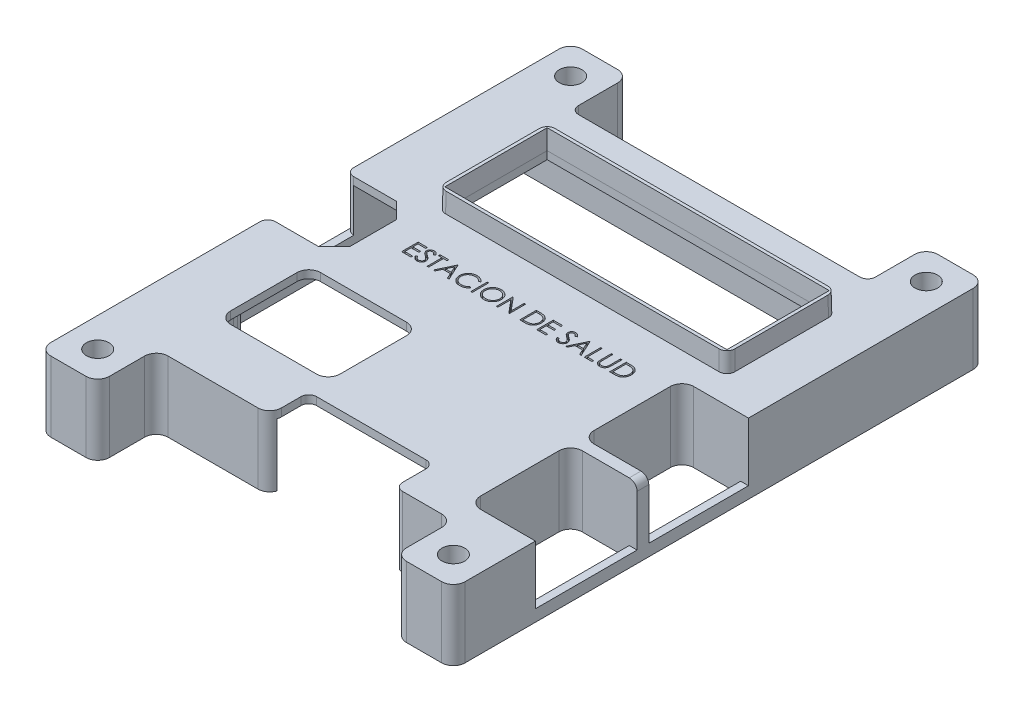
SolidWorks part; units mm, degrees
material "PVC 0.007 Plasticized"
ref_plane "Front Plane" through (0, 0, 0) normal (0, 0, 1) x (1, 0, 0)
ref_plane "Top Plane" through (0, 0, 0) normal (0, 1, 0) x (1, 0, 0)
ref_plane "Right Plane" through (0, 0, 0) normal (1, 0, 0) x (0, 0, -1)
sketch "Sketch1" plane through (0, 0, 0) normal (0, 1, 0) x (1, 0, 0)
  line L1 (-53, -53) -> (53, -53)
  line L2 (-53, -53) -> (-53, 53)
  line L3 (-53, 53) -> (53, 53)
  line L4 (53, -53) -> (53, 53)
  line L5 (-53, -53) -> (53, 53) construction
  line L6 (-53, 53) -> (53, -53) construction
  point P0 (0, 0)
  dimension "D1" = 106
  dimension "D2" = 106
extrude "Boss-Extrude1" add sketch "Sketch1" along normal blind 18
sketch "Sketch2" plane through (0, 18, 0) normal (0, 1, 0) x (1, 0, 0)
  line L0 (53, -53) -> (53, 53) construction
  line L1 (53, 7.5) -> (36, 7.5)
  line L2 (53, 7.5) -> (53, -18)
  line L3 (53, -18) -> (36, -18)
  line L4 (36, 7.5) -> (36, -18)
  line L5 (53, 53) -> (-53, 53) construction
  line L6 (-53, -53) -> (53, -53) construction
  dimension "D1" = 45.5
  dimension "D2" = 35
  dimension "D3" = 17
extrude "Cut-Extrude1" cut sketch "Sketch2" against normal through all
sketch "Sketch3" plane through (0, 18, 0) normal (0, 1, 0) x (1, 0, 0)
  line L0 (53, -53) -> (53, -18) construction
  line L1 (53, -21) -> (36, -21)
  line L2 (53, -21) -> (53, -47)
  line L3 (53, -47) -> (36, -47)
  line L4 (36, -21) -> (36, -47)
  line L5 (-53, -53) -> (53, -53) construction
  line L8 (36, -18) -> (53, -18) construction
  line L10 (36, 7.5) -> (36, -18) construction
  dimension "D1" = 6
  dimension "D2" = 3
extrude "Cut-Extrude2" cut sketch "Sketch3" against normal through all
shell "Shell1" thickness 2 removed face at (29.6667, 0, 13.0833)
sketch "Sketch5" plane through (-53, 0, 0) normal (-1, 0, 0) x (0, 0, 1)
  line L0 (-53, 0) -> (53, 0) construction
  line L1 (-10.5, 0) -> (9.5, 0)
  line L2 (-10.5, 0) -> (-10.5, 25)
  line L3 (-10.5, 25) -> (9.5, 25)
  line L4 (9.5, 0) -> (9.5, 25)
  line L5 (-53, 18) -> (-53, 0) construction
  dimension "D1" = 42.5
  dimension "D2" = 20
  dimension "D3" = 25
extrude "Cut-Extrude3" cut sketch "Sketch5" against normal blind 17
sketch "Sketch6" plane through (0, 0, 53) normal (0, 0, 1) x (1, 0, 0)
  line L0 (-53, 0) -> (53, 0) construction
  line L1 (-15, 0) -> (23, 0)
  line L2 (-15, 0) -> (-15, 18)
  line L3 (-15, 18) -> (23, 18)
  line L4 (23, 0) -> (23, 18)
  line L5 (53, 18) -> (53, 0) construction
  line L6 (-53, 18) -> (-53, 0) construction
  line L7 (-53, 18) -> (53, 18) construction
  dimension "D1" = 30
  dimension "D2" = 38
extrude "Cut-Extrude4" cut sketch "Sketch6" against normal blind 10
sketch "Sketch8" plane through (0, 18, 0) normal (0, 1, 0) x (1, 0, 0)
  line L0 (-9, -53) -> (-9, -15)
  line L1 (-9, -15) -> (-37, -15)
  line L2 (-9, -53) -> (-37, -53)
  line L3 (-37, -15) -> (-37, -53)
  line L6 (-53, 53) -> (-53, 10.5) construction
  line L7 (-53, -53) -> (-15, -53) construction
  line L10 (-53, -9.5) -> (-53, -53) construction
  dimension "D1" = 38
  dimension "D2" = 16
  dimension "D3" = 44
extrude "Cut-Extrude5" cut sketch "Sketch8" against normal through all
sketch "Sketch9" plane through (0, 18, 0) normal (0, 1, 0) x (1, 0, 0)
  line L0 (53, 53) -> (-53, 53) construction
  line L1 (-32, 41) -> (40, 41)
  line L2 (-32, 41) -> (-32, 15)
  line L3 (-32, 15) -> (40, 15)
  line L4 (40, 41) -> (40, 15)
  line L5 (53, 7.5) -> (53, 53) construction
  dimension "D1" = 72
  dimension "D2" = 26
  dimension "D3" = 12
  dimension "D4" = 13
extrude "Extrude-Thin1" add sketch "Sketch9" along normal blind 5 draft 1 thin thin type one direction wall 1
sketch "Sketch10" plane through (0, 18, 0) normal (0, 1, 0) x (1, 0, 0)
  line L8 (40, 41) -> (-32, 41)
  line L9 (-32, 41) -> (-32, 15)
  line L10 (-32, 15) -> (40, 15)
  line L11 (40, 15) -> (40, 41)
  line L12 (40, 41) -> (-32, 41)
  line L13 (-32, 41) -> (-32, 15)
  line L14 (-32, 15) -> (40, 15)
  line L15 (40, 15) -> (40, 41)
  dimension "D1" = 0
extrude "Cut-Extrude6" cut sketch "Sketch10" against normal up to next
chamfer "Chamfer1" distance 4 angle 45 2 edges at (-36, 17, -10.5) (-36, 17, 9.5)
sketch "Sketch12" plane through (0, 0, 0) normal (0, 1, 0) x (1, 0, 0)
  line L0 (0, 53) -> (0, -52.3512) construction
  line L1 (53, 53) -> (-53, 53) construction
  line L2 (-52.4973, 0) -> (53.7635, 0) construction
  line L15 (-38, 53) -> (-53, 53)
  line L16 (-53, 68) -> (-53, 53)
  line L17 (-38, 68) -> (-53, 68)
  line L18 (-38, 68) -> (-38, 53)
  line L32 (-53, 53) -> (-53, 10.5) construction
  line L33 (38, 68) -> (38, 53)
  line L34 (38, 68) -> (53, 68)
  line L35 (53, 68) -> (53, 53)
  line L36 (38, 53) -> (53, 53)
  line L37 (38, -53) -> (53, -53)
  line L38 (53, -68) -> (53, -53)
  line L39 (38, -68) -> (53, -68)
  line L40 (38, -68) -> (38, -53)
  line L41 (-38, -68) -> (-38, -53)
  line L42 (-38, -68) -> (-53, -68)
  line L43 (-53, -68) -> (-53, -53)
  line L44 (-38, -53) -> (-53, -53)
  dimension "D1" = 15
  dimension "D2" = 15
extrude "Boss-Extrude2" add sketch "Sketch12" along normal up to surface (18 mm away) up to face at (2.1667, 18, 15.6667)
sketch "Sketch13" plane through (0, 18, 0) normal (0, 1, 0) x (1, 0, 0)
  line L18 (-38, 53) -> (-53, 53) construction
  line L19 (-53, 68) -> (-53, 10.5) construction
  line L21 (-45.5, 68) -> (-45.5, 53) construction
  line L22 (-53, 68) -> (-38, 68) construction
  line L24 (0, -12.65) -> (0, 12.65) construction
  line L25 (-12.65, 0) -> (12.65, 0) construction
  circle A4 centre (-45.5, 60.5) radius 7.5 construction
  circle A5 centre (45.5, 60.5) radius 7.5 construction
  circle A6 centre (45.5, -60.5) radius 7.5 construction
  circle A7 centre (-45.5, -60.5) radius 7.5 construction
  point P54 (-45.5, 60.5)
  point P59 (45.5, 60.5)
  point P63 (45.5, -60.5)
  point P65 (-45.5, -60.5)
hole_wizard "M5 Clearance Hole1" positions "Sketch13" profile "Sketch14" hole size "M5" standard "ANSI Metric" end condition through all
sketch "Sketch14" plane through (-45.5, 18, 60.5) normal (1, 0, 0) x (0, 0, 1)
  line L0 (0, 0) -> (0, 18)
  line L1 (0, 18) -> (2.9, 18)
  line L2 (2.9, 18) -> (2.9, 0)
  line L5 (2.9, 0) -> (0, 0)
  line L11 (0, -6.35) -> (0, 107.95) construction
  dimension "Thru Hole Dia." = 5.8
  dimension "Thru Hole Depth" = 18
sketch "Sketch15" plane through (0, 18, 0) normal (0, 1, 0) x (1, 0, 0)
  line L0 (-9, -43) -> (-9, -15) construction
  line L1 (-9, -38) -> (-38, -38)
  line L2 (-9, -38) -> (-9, -53)
  line L3 (-9, -53) -> (-38, -53)
  line L4 (-38, -38) -> (-38, -53)
  line L5 (-38, -53) -> (-38, -68) construction
  line L6 (23, -43) -> (-9, -43) construction
  line L7 (-38, -53) -> (-37, -53) construction
  dimension "D1" = 5
extrude "Boss-Extrude3" add sketch "Sketch15" against normal up to surface (2 mm away) up to face at (4, 16, -28)
sketch "Sketch22" plane through (0, 16, 0) normal (0, -1, 0) x (1, 0, 0)
  line L1 (-37, 51) -> (-9, 51)
  line L2 (-37, 51) -> (-37, 53)
  line L3 (-37, 53) -> (-9, 53)
  line L4 (-9, 51) -> (-9, 53)
extrude "Boss-Extrude7" add sketch "Sketch22" along normal up to surface (16 mm away)
sketch "Sketch16" plane through (0, 18, 0) normal (0, 1, 0) x (1, 0, 0)
  line L0 (-36, 0) -> (36, 0) construction
  line L1 (-36, 6.5) -> (-36, -5.5) construction
  line L2 (36, 7.5) -> (36, -18) construction
  text T0 "ESTACION DE SALUD" font "Century Gothic" height in points 16
extrude "Cut-Extrude8" cut sketch "Sketch16" against normal blind 1.5
sketch "Sketch17" plane through (0, 16, 0) normal (0, -1, 0) x (1, 0, 0)
  line L0 (-51, 25.25) -> (-45, 25.25)
  line L1 (-51, 9.5) -> (-51, 51) construction
  line L2 (-43, 27.25) -> (-43, 28.25)
  line L3 (-45, 30.25) -> (-51, 30.25)
  line L4 (-51, 9.5) -> (-51, 51) construction
  line L5 (-51, 30.25) -> (-51, 25.25)
  arc A0 (-43, 28.25) -> (-45, 30.25) centre (-45, 28.25) ccw
  arc A1 (-45, 25.25) -> (-43, 27.25) centre (-45, 27.25) ccw
  point P5 (-40.3391, 29.0858)
  point P11 (-43, 30.25)
  point P14 (-43, 25.25)
  dimension "D3" = 2
  dimension "D1" = 5
  dimension "D2" = 8
extrude "Boss-Extrude4" add sketch "Sketch17" along normal up to surface (16 mm away)
sketch "Sketch19" plane through (-53, 0, 0) normal (-1, 0, 0) x (0, 0, 1)
  line L0 (-10.5, 18) -> (-10.5, 0) construction
  line L1 (-10.5, 5) -> (9.5, 5)
  line L2 (-10.5, 5) -> (-10.5, 0)
  line L3 (-10.5, 0) -> (9.5, 0)
  line L4 (9.5, 5) -> (9.5, 0)
  dimension "D1" = 5
extrude "Boss-Extrude5" add sketch "Sketch19" against normal up to surface (2 mm away) up to face at (-51, 8, -30.75)
sketch "Sketch20" plane through (53, 0, 0) normal (1, 0, 0) x (0, 0, -1)
  line L1 (-49.5, 3) -> (10.5, 3)
  line L2 (-49.5, 3) -> (-49.5, 0)
  line L3 (-49.5, 0) -> (10.5, 0)
  line L4 (10.5, 3) -> (10.5, 0)
  line L5 (7.5, 0) -> (-18, 0) construction
  line L6 (-19.5, 18) -> (-19.5, 0) construction
  line L7 (-21, 18) -> (-18, 18) construction
  dimension "D1" = 3
  dimension "D2" = 60
extrude "Boss-Extrude6" add sketch "Sketch20" against normal blind 2
fillet "Fillet8" radius 2 12 edges at (-32.9564, 20.5, -14.0436) (-32.9564, 20.5, -41.9564) (40.9564, 20.5, -41.9564) (40.9564, 20.5, -14.0436) (23, 9, 53) (23, 17, 43) (-9, 17, 43) (38, 9, -53) (-38, 9, -53) (-53, 11.5, 9.5) (-53, 11.5, -10.5) (53, 18, 19.5)
fillet "Fillet1" radius 3 4 edges at (36, 9, 47) (36, 9, 21) (36, 9, 18) (36, 9, -7.5)
fillet "Fillet5" radius 3 11 edges at (-9, 9, 53) (-38, 9, -68) (-53, 9, -68) (38, 9, -68) (53, 9, -68) (53, 9, 68) (38, 9, 68) (38, 9, 53) (-38, 9, 68) (-53, 9, 68) (-38, 9, 53)
fillet "Fillet4" radius 3 4 edges at (-37, 17, 15) (-9, 17, 38) (-37, 17, 38) (-9, 17, 15)
sketch "Sketch23" plane through (0, 0, 0) normal (0, -1, 0) x (1, 0, 0)
  line L0 (23, 51) -> (51, 51) construction
  line L1 (51, 51) -> (51, 49) construction
  line L2 (34, 49) -> (51, 49) construction
  line L3 (34, 51) -> (51, 51)
  line L4 (51, 51) -> (51, 49)
  line L5 (34, 49) -> (51, 49)
  line L6 (34, 49) -> (34, 51)
extrude "Boss-Extrude8" add sketch "Sketch23" against normal up to surface (16 mm away)
